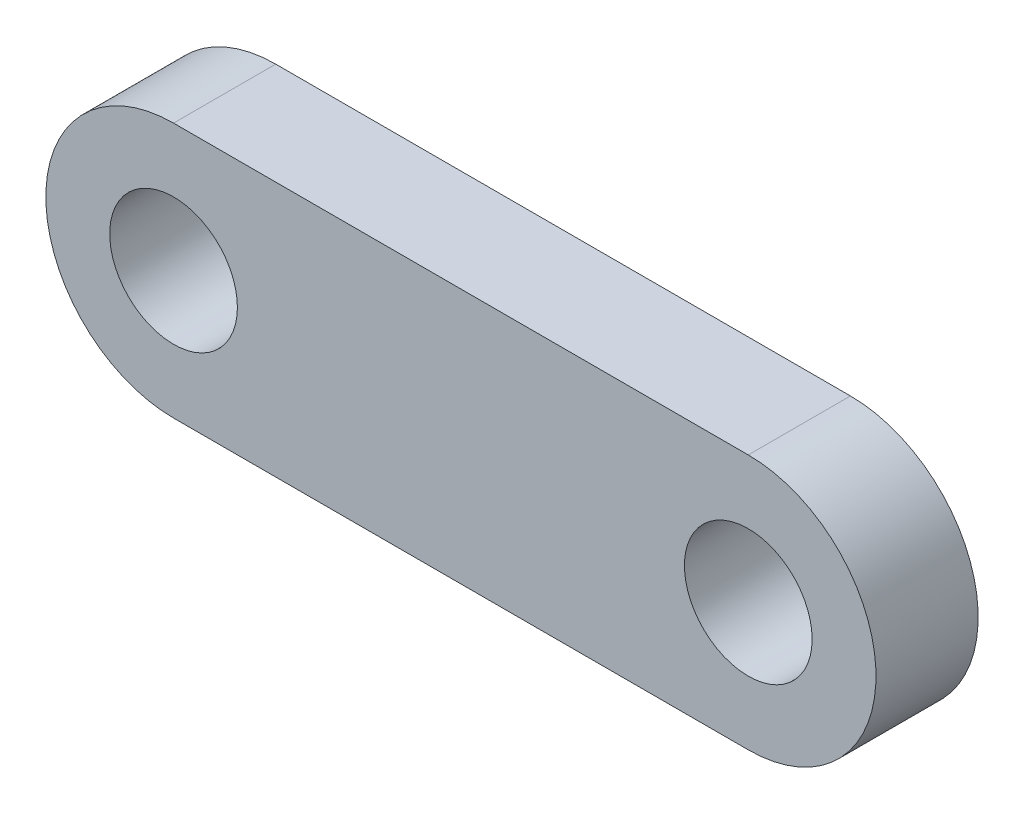
SolidWorks part; units mm, degrees
material "ABS"
ref_plane "Front Plane" through (0, 0, 0) normal (0, 0, 1) x (1, 0, 0)
ref_plane "Top Plane" through (0, 0, 0) normal (0, 1, 0) x (1, 0, 0)
ref_plane "Right Plane" through (0, 0, 0) normal (1, 0, 0) x (0, 0, -1)
sketch "Sketch1" plane through (0, 0, 0) normal (0, 0, 1) x (1, 0, 0)
  line L0 (0, 3.175) -> (14.2875, 3.175)
  line L1 (0, -3.175) -> (14.2875, -3.175)
  circle A0 centre (0, 0) radius 1.5875
  circle A1 centre (0, 0) radius 3.175
  circle A2 centre (14.2875, 0) radius 1.5875
  circle A3 centre (14.2875, 0) radius 3.175
  dimension "D1" = 3.175
  dimension "D2" = 6.35
  dimension "D3" = 14.2875
extrude "Boss-Extrude1" add sketch "Sketch1" along normal blind 2.54 contours A3 L0 A1 L1 | A1 A0 | A3 A2 region at (7.1437, 0, 0) region at (2.1816, 2.1816, 0) region at (16.4691, 2.1816, 0)
